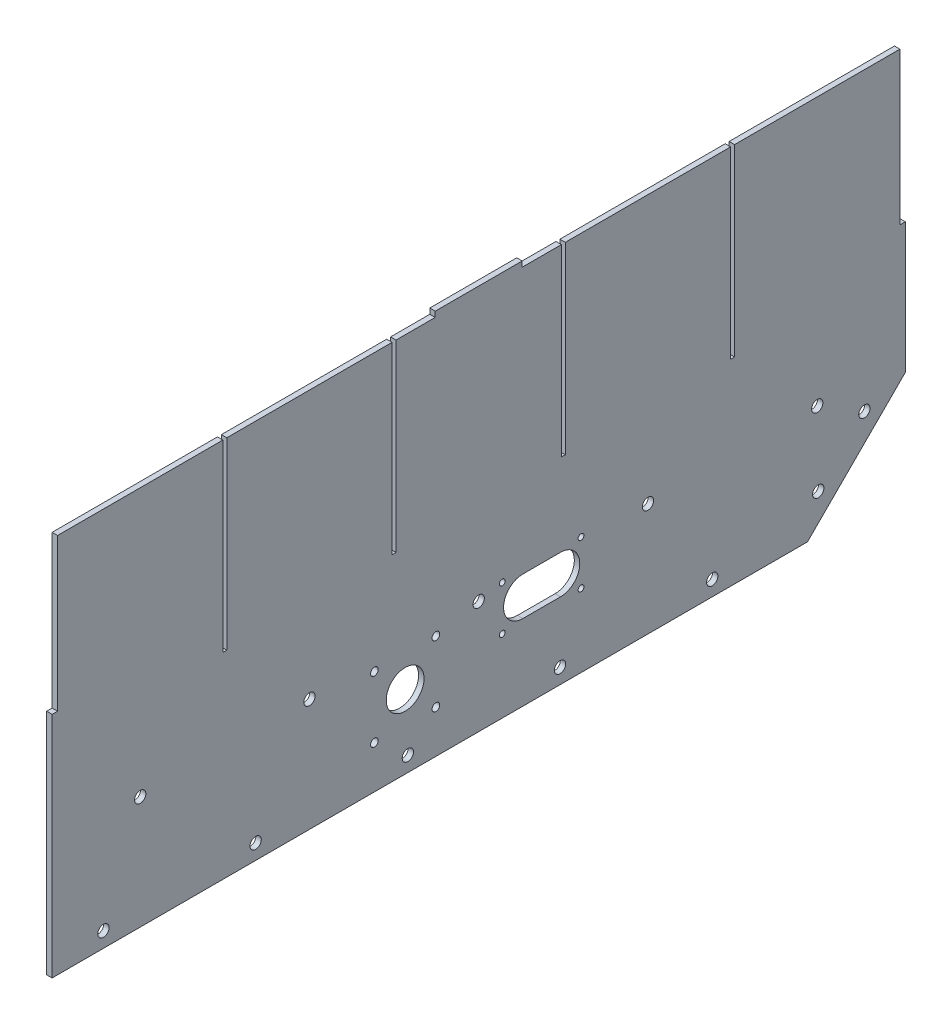
SolidWorks part; units mm, degrees
material "6061-T6 (SS)"
ref_plane "X-Y Datum" through (0, 0, 0) normal (0, 0, 1) x (1, 0, 0)
ref_plane "X-Z Datum" through (0, 0, 0) normal (0, 1, 0) x (1, 0, 0)
ref_plane "Y-Z Datum" through (0, 0, 0) normal (1, 0, 0) x (0, 0, -1)
sketch "Sketch1" plane through (0, 0, 0) normal (1, 0, 0) x (0, 0, -1)
  line L1 (-249.174, 82.55) -> (249.174, 82.55)
  line L2 (-249.174, 82.55) -> (-249.174, -82.55)
  line L3 (-249.174, -82.55) -> (249.174, -82.55)
  line L4 (249.174, 82.55) -> (249.174, -82.55)
  line L5 (-249.174, 82.55) -> (249.174, -82.55) construction
  line L6 (-249.174, -82.55) -> (249.174, 82.55) construction
  point P0 (0, 0)
  dimension "D1" = 165.1
  dimension "D2" = 498.348
extrude "Boss-Extrude1" add sketch "Sketch1" along normal mid plane 3.175
sketch "Sketch2" plane through (1.5875, 0, 0) normal (1, 0, 0) x (0, 0, -1)
  line L2 (249.174, -82.55) -> (192.024, -139.7)
  line L5 (-249.174, -82.55) -> (249.174, -82.55) construction
  line L6 (-249.174, -82.55) -> (249.174, -82.55)
  line L8 (192.024, -139.7) -> (-249.174, -139.7)
  line L9 (-249.174, -139.7) -> (-249.174, -82.55)
  line L11 (-249.174, 82.55) -> (-249.174, -82.55) construction
  line L12 (249.174, -82.55) -> (249.174, 82.55) construction
  line M10 (-249.174, -82.55) -> (249.174, -82.55)
  dimension "D1" = 45
  dimension "D5" = 57.15
extrude "Boss-Extrude2" add sketch "Sketch2" against normal blind 3.175 contours L2 M10 region at (1.5875, -110.5456, 13.9978)
sketch "Sketch3" plane through (-1.5875, 0, 0) normal (-1, 0, 0) x (0, 0, 1)
  line L0 (219.202, -139.7) -> (219.202, -130.81)
  line L1 (-192.024, -139.7) -> (249.174, -139.7) construction
  line L2 (219.202, -130.81) -> (249.174, -130.81)
  line L3 (249.174, 82.55) -> (249.174, -139.7) construction
  circle A0 centre (219.202, -130.81) radius 3.302
  dimension "D1" = 6.604
extrude "Cut-Extrude1" cut sketch "Sketch3" against normal through all contours L0 A0 L2 | L2 A0 L0 region at (-1.5875, -130.3429, 218.7349) region at (-1.5875, -132.2114, 220.6034)
pattern_linear "LPattern1" count 5 spacing 88.9 along (0, 0, -1) of "Cut-Extrude1"
sketch "Sketch4" plane through (-1.5875, 0, 0) normal (-1, 0, 0) x (0, 0, 1)
  line L0 (-206.3924, -125.3316) -> (-198.3102, -117.2494)
  line L1 (-249.174, -82.55) -> (-192.024, -139.7) construction
  line L2 (-192.024, -139.7) -> (-183.9418, -131.6178)
  line L3 (-183.9418, -131.6178) -> (-198.3102, -117.2494)
  circle A0 centre (-198.3102, -117.2494) radius 3.302
  dimension "D1" = 6.604
extrude "Cut-Extrude2" cut sketch "Sketch4" against normal through all and the other way through all contours L3 A0 L0 | L0 A0 L3 region at (-1.5875, -116.5887, -198.3102) region at (-1.5875, -119.2313, -198.3102)
pattern_linear "LPattern2" count 2 spacing 38.1 along (0, 0.7071, -0.7071) of "Cut-Extrude2"
sketch "Sketch5" plane through (1.5875, 0, 0) normal (1, 0, 0) x (0, 0, -1)
  line L0 (245.872, 82.677) -> (245.872, -6.477)
  line L1 (249.174, 82.55) -> (245.999, 82.55)
  line L2 (249.174, 82.55) -> (249.174, -6.35)
  line L3 (249.174, -6.35) -> (245.999, -6.35)
  line L4 (245.999, 82.55) -> (245.999, -6.35)
  line L5 (-249.174, 82.55) -> (-245.999, 82.55)
  line L6 (-249.174, 82.55) -> (-249.174, -6.35)
  line L7 (-249.174, -6.35) -> (-245.999, -6.35)
  line L8 (-245.999, 82.55) -> (-245.999, -6.35)
  line L9 (249.301, -6.477) -> (245.872, -6.477)
  line L10 (249.301, 82.677) -> (249.301, -6.477)
  line L11 (249.301, 82.677) -> (245.872, 82.677)
  line L12 (-245.872, 82.677) -> (-245.872, -6.477)
  line L13 (-249.301, -6.477) -> (-245.872, -6.477)
  line L14 (-249.301, 82.677) -> (-249.301, -6.477)
  line L15 (-249.301, 82.677) -> (-245.872, 82.677)
  line M6 (249.174, -82.55) -> (249.174, 82.55)
  line M7 (249.174, 82.55) -> (-249.174, 82.55)
  line M8 (-249.174, 82.55) -> (-249.174, -139.7)
  dimension "D1" = 3.175
  dimension "D2" = 88.9
  dimension "D3" = 3.175
  dimension "D4" = 88.9
  dimension "D5" = 0.127
extrude "Cut-Extrude3" cut sketch "Sketch5" against normal through all contours L4 L3 M7 M6 | L8 L7 M7 M8 region at (1.5875, 38.1, -247.5865) region at (1.5875, 38.1, 247.5865)
sketch "Sketch6" plane through (1.5875, 0, 0) normal (1, 0, 0) x (0, 0, -1)
  line L0 (149.5933, 82.7151) -> (146.9771, 82.7151)
  line L1 (149.4282, -24.892) -> (149.4282, 82.55) construction
  line L2 (122.174, 82.55) -> (249.174, 82.55)
  line L3 (149.4282, -24.892) -> (149.4282, 82.55)
  line L4 (146.9771, 82.7151) -> (146.9771, -25.0571)
  line L5 (149.4282, 82.55) -> (147.1422, 82.55)
  line L6 (149.4282, 82.55) -> (149.4282, -24.892)
  line L7 (149.4282, -24.892) -> (147.1422, -24.892)
  line L8 (147.1422, 82.55) -> (147.1422, -24.892)
  line L9 (149.5933, -25.0571) -> (146.9771, -25.0571)
  line L10 (149.5933, 82.7151) -> (149.5933, -25.0571)
  dimension "D1" = 2.286
  dimension "D2" = 107.442
  dimension "D3" = 0.1651
extrude "Cut-Extrude4" cut sketch "Sketch6" against normal through all contours L2 L8 L7 L3 region at (1.5875, 28.829, -148.2852)
pattern_linear "LPattern3" count 4 spacing 98.8568 along (0, 0, 1) of "Cut-Extrude4"
sketch "Sketch8" plane through (1.5875, 0, 0) normal (1, 0, 0) x (0, 0, -1)
  line L0 (122.174, 85.725) -> (25.4, 85.725) construction
  line L1 (25.4, 82.55) -> (-25.4, 82.55)
  line L2 (25.4, 82.55) -> (25.4, 85.725)
  line L3 (25.4, 85.725) -> (-25.4, 85.725)
  line L4 (-25.4, 82.55) -> (-25.4, 85.725)
  line L5 (25.4, 82.55) -> (-25.4, 85.725) construction
  line L6 (25.4, 85.725) -> (-25.4, 82.55) construction
  point P0 (0, 84.1375)
  dimension "D1" = 3.175
  dimension "D2" = 50.8
extrude "Boss-Extrude3" add sketch "Sketch8" against normal blind 3.175
sketch "Sketch9" plane through (1.5875, 0, 0) normal (1, 0, 0) x (0, 0, -1)
  line L0 (-249.174, -6.35) -> (-249.174, -139.7) construction
  line L1 (192.024, -139.7) -> (-249.174, -139.7) construction
  circle A0 centre (-42.9768, -96.7994) radius 11.05
  dimension "D3" = 22.1
  dimension "D1" = 206.1972
  dimension "D2" = 42.9006
extrude "Cut-Extrude5" cut sketch "Sketch9" against normal through all
sketch "Sketch10" plane through (1.5875, 0, 0) normal (1, 0, 0) x (0, 0, -1)
  line L0 (192.024, -139.7) -> (-249.174, -139.7) construction
  circle A0 centre (0, -73.8124) radius 3
  dimension "D2" = 6
  dimension "D1" = 65.8876
hole_wizard "M6 Clearance Hole1" positions "Sketch11" profile "Sketch12" hole size "M6" standard "ANSI Metric" end condition through all
sketch "Sketch11" plane through (1.5875, 0, 0) normal (1, 0, 0) x (0, 0, -1)
  point P0 (0, -73.8124)
sketch "Sketch12" plane through (1.5875, -73.8124, 0) normal (0, 1, 0) x (0, 0, -1)
  line L0 (0, 0) -> (0, 3.175)
  line L1 (0, 3.175) -> (3.3, 3.175)
  line L2 (3.3, 3.175) -> (3.3, 0)
  line L5 (3.3, 0) -> (0, 0)
  line L11 (0, -6.35) -> (0, 107.95) construction
  dimension "Thru Hole Dia." = 6.6
  dimension "Thru Hole Depth" = 3.175
pattern_linear "LPattern4" count 3 spacing 98.8568 along (0, 0, 1) count 3 spacing 98.8568 along (0, 0, -1) of "M6 Clearance Hole1"
sketch "Sketch14" plane through (1.5875, 0, 0) normal (1, 0, 0) x (0, 0, -1)
  line L0 (192.024, -139.7) -> (-249.174, -139.7) construction
  line L1 (59.7662, -97.1042) -> (13.7662, -97.1042)
  line L2 (59.7662, -97.1042) -> (59.7662, -71.1042)
  line L3 (59.7662, -71.1042) -> (13.7662, -71.1042)
  line L4 (13.7662, -97.1042) -> (13.7662, -71.1042)
  line L5 (59.7662, -97.1042) -> (13.7662, -71.1042) construction
  line L6 (59.7662, -71.1042) -> (13.7662, -97.1042) construction
  line L7 (249.174, -82.55) -> (249.174, -6.35) construction
  line L8 (59.7662, -84.1042) -> (13.7662, -84.1042) construction
  line L9 (-25.0163, -114.7599) -> (-60.9373, -114.7599)
  line L10 (-25.0163, -114.7599) -> (-25.0163, -78.8389)
  line L11 (-25.0163, -78.8389) -> (-60.9373, -78.8389)
  line L12 (-60.9373, -114.7599) -> (-60.9373, -78.8389)
  line L13 (-25.0163, -114.7599) -> (-60.9373, -78.8389) construction
  line L14 (-25.0163, -78.8389) -> (-60.9373, -114.7599) construction
  line L15 (47.7662, -84.1042) -> (25.7662, -84.1042)
  line L16 (47.7662, -95.3542) -> (25.7662, -95.3542)
  line L17 (47.7662, -72.8542) -> (25.7662, -72.8542)
  arc A1 (47.7662, -95.3542) -> (47.7662, -72.8542) centre (47.7662, -84.1042) ccw
  arc A2 (25.7662, -72.8542) -> (25.7662, -95.3542) centre (25.7662, -84.1042) ccw
  point P0 (36.7662, -84.1042)
  point P10 (-42.9768, -96.7994)
  point P20 (36.7662, -84.1042)
  dimension "D7" = 11.25
  dimension "D1" = 46
  dimension "D2" = 26
  dimension "D3" = 42.5958
  dimension "D4" = 189.4078
  dimension "D5" = 35.921
  dimension "D6" = 22
hole_wizard "M4 Clearance Hole1" positions "Sketch17" profile "Sketch18" hole size "M4" standard "ANSI Metric" end condition through all
sketch "Sketch17" plane through (1.5875, 0, 0) normal (1, 0, 0) x (0, 0, -1)
  point P0 (-25.0163, -78.8389)
  point P3 (-60.9373, -78.8389)
  point P6 (-60.9373, -114.7599)
  point P9 (-25.0163, -114.7599)
sketch "Sketch18" plane through (1.5875, -78.8389, 25.0163) normal (0, 1, 0) x (0, 0, -1)
  line L0 (0, 0) -> (0, 3.175)
  line L1 (0, 3.175) -> (2.25, 3.175)
  line L2 (2.25, 3.175) -> (2.25, 0)
  line L5 (2.25, 0) -> (0, 0)
  line L11 (0, -6.35) -> (0, 107.95) construction
  dimension "Thru Hole Dia." = 4.5
  dimension "Thru Hole Depth" = 3.175
extrude "Cut-Extrude6" cut sketch "Sketch14" against normal through all contours L17 A2 L16 A1 region at (1.5875, -94.8556, -36.7662)
hole_wizard "M3 Clearance Hole1" positions "Sketch19" profile "Sketch20" hole size "M3" standard "ANSI Metric" end condition through all
sketch "Sketch19" plane through (1.5875, 0, 0) normal (1, 0, 0) x (0, 0, -1)
  point P0 (59.7662, -97.1042)
  point P3 (59.7662, -71.1042)
  point P6 (13.7662, -71.1042)
  point P9 (13.7662, -97.1042)
sketch "Sketch20" plane through (1.5875, -97.1042, -59.7662) normal (0, 1, 0) x (0, 0, -1)
  line L0 (0, 0) -> (0, 3.175)
  line L1 (0, 3.175) -> (1.7, 3.175)
  line L2 (1.7, 3.175) -> (1.7, 0)
  line L5 (1.7, 0) -> (0, 0)
  line L11 (0, -6.35) -> (0, 107.95) construction
  dimension "Thru Hole Dia." = 3.4
  dimension "Thru Hole Depth" = 3.175
sketch "Sketch21" plane through (1.5875, 0, 0) normal (1, 0, 0) x (0, 0, -1)
  line L0 (36.7662, -72.8542) -> (36.7662, -95.3542)
  line L1 (47.7662, -72.8542) -> (25.7662, -72.8542) construction
  line L2 (47.7662, -95.3542) -> (25.7662, -95.3542) construction
  line L4 (1.8412, -61.8792) -> (71.6912, -61.8792)
  line L5 (1.8412, -61.8792) -> (1.8412, -106.3292)
  line L6 (1.8412, -106.3292) -> (71.6912, -106.3292)
  line L7 (71.6912, -61.8792) -> (71.6912, -106.3292)
  line L8 (1.8412, -61.8792) -> (71.6912, -106.3292) construction
  line L9 (1.8412, -106.3292) -> (71.6912, -61.8792) construction
  line L38 (50.5714, 82.55) -> (50.5714, -24.892)
  line L40 (50.5714, 82.55) -> (50.5714, -24.892)
  line L41 (48.2854, 82.55) -> (25.4, 82.55)
  line L42 (25.4, 82.55) -> (25.4, 85.725)
  line L43 (25.4, 85.725) -> (-25.4, 85.725)
  line L44 (-25.4, 85.725) -> (-25.4, 82.55)
  line L45 (-25.4, 82.55) -> (-48.2854, 82.55)
  line L47 (50.5714, -24.892) -> (48.2854, -24.892)
  line L49 (50.5714, -24.892) -> (48.2854, -24.892)
  line L51 (48.2854, -24.892) -> (48.2854, 82.55)
  line L53 (48.2854, -24.892) -> (48.2854, 82.55)
  line L54 (-149.4282, 82.55) -> (-245.999, 82.55)
  line L56 (-249.174, -6.35) -> (-249.174, -139.7)
  line L57 (-249.174, -139.7) -> (192.024, -139.7)
  line L58 (192.024, -139.7) -> (249.174, -82.55)
  line L59 (249.174, -82.55) -> (249.174, -6.35)
  line L60 (-149.4282, 82.55) -> (-245.999, 82.55)
  line L63 (-48.2854, 82.55) -> (-48.2854, -24.892)
  line L65 (-48.2854, 82.55) -> (-48.2854, -24.892)
  line L70 (48.2854, 82.55) -> (25.4, 82.55)
  line L71 (25.4, 82.55) -> (25.4, 85.725)
  line L72 (25.4, 85.725) -> (-25.4, 85.725)
  line L73 (-25.4, 85.725) -> (-25.4, 82.55)
  line L74 (-25.4, 82.55) -> (-48.2854, 82.55)
  line L85 (-249.174, -6.35) -> (-249.174, -139.7)
  line L86 (-249.174, -139.7) -> (192.024, -139.7)
  line L87 (192.024, -139.7) -> (249.174, -82.55)
  line L88 (249.174, -82.55) -> (249.174, -6.35)
  line L96 (-245.999, 82.55) -> (-245.999, -6.35)
  line L98 (-245.999, 82.55) -> (-245.999, -6.35)
  line L100 (-48.2854, -24.892) -> (-50.5714, -24.892)
  line L102 (-48.2854, -24.892) -> (-50.5714, -24.892)
  line L104 (-50.5714, -24.892) -> (-50.5714, 82.55)
  line L106 (-245.999, -6.35) -> (-249.174, -6.35)
  line L108 (-245.999, -6.35) -> (-249.174, -6.35)
  line L110 (-50.5714, -24.892) -> (-50.5714, 82.55)
  line L112 (-50.5714, 82.55) -> (-147.1422, 82.55)
  line L114 (-50.5714, 82.55) -> (-147.1422, 82.55)
  line L116 (249.174, -6.35) -> (245.999, -6.35)
  line L117 (249.174, -6.35) -> (245.999, -6.35)
  line L118 (245.999, -6.35) -> (245.999, 82.55)
  line L119 (245.999, -6.35) -> (245.999, 82.55)
  line L120 (245.999, 82.55) -> (149.4282, 82.55)
  line L121 (245.999, 82.55) -> (149.4282, 82.55)
  line L122 (-147.1422, 82.55) -> (-147.1422, -24.892)
  line L123 (-147.1422, 82.55) -> (-147.1422, -24.892)
  line L124 (-147.1422, -24.892) -> (-149.4282, -24.892)
  line L125 (-147.1422, -24.892) -> (-149.4282, -24.892)
  line L126 (-149.4282, -24.892) -> (-149.4282, 82.55)
  line L127 (-149.4282, -24.892) -> (-149.4282, 82.55)
  line L128 (149.4282, 82.55) -> (149.4282, -24.892)
  line L129 (149.4282, 82.55) -> (149.4282, -24.892)
  line L130 (149.4282, -24.892) -> (147.1422, -24.892)
  line L131 (149.4282, -24.892) -> (147.1422, -24.892)
  line L132 (147.1422, -24.892) -> (147.1422, 82.55)
  line L133 (147.1422, -24.892) -> (147.1422, 82.55)
  line L134 (147.1422, 82.55) -> (50.5714, 82.55)
  line L135 (147.1422, 82.55) -> (50.5714, 82.55)
  point P6 (36.7662, -84.1042)
  dimension "D1" = 69.85
  dimension "D2" = 44.45
  dimension "D3" = 0
extrude "Cut-Extrude7" [suppressed] cut sketch "Sketch21" against normal through all contours L133 L135 L40 L49 L53 L70 L71 L72 L73 L74 L65 L102 L110 L114 L123 L125 L127 L60 L98 L108 L85 L86 L87 L88 L117 L119 L121 L129 L131 L4 L7 L6 L5
